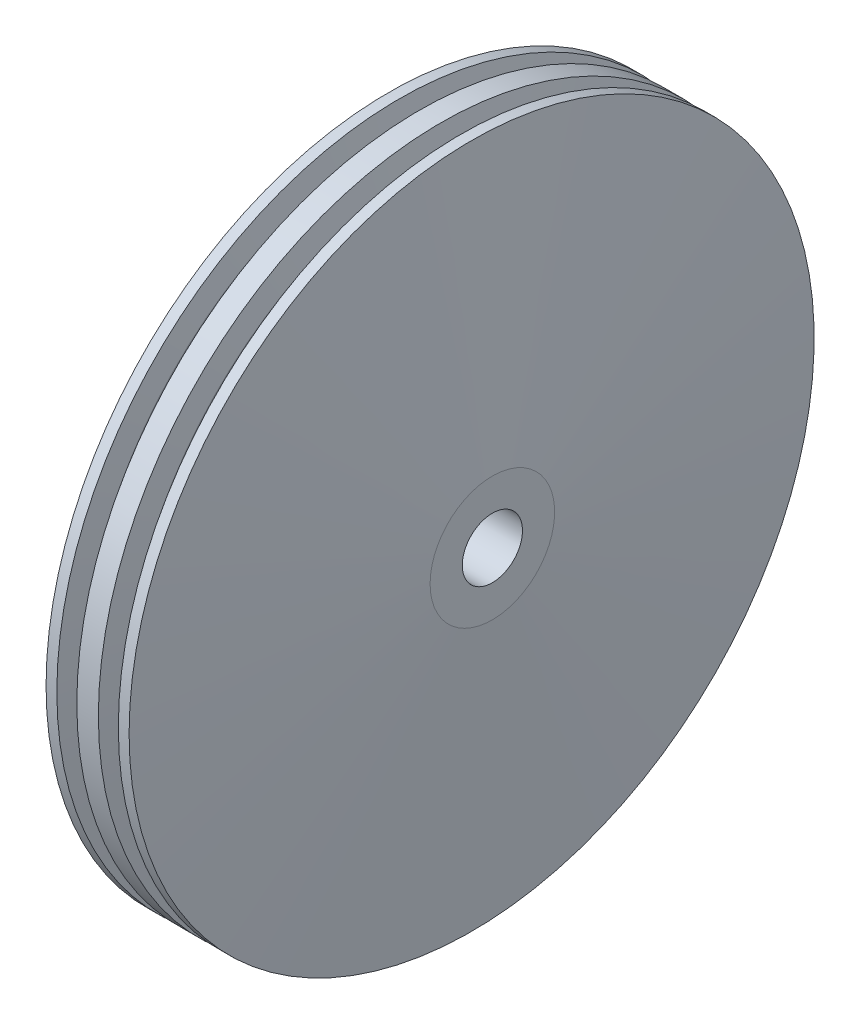
SolidWorks part; units mm, degrees
ref_plane "Plan de face" through (0, 0, 0) normal (0, 0, 1) x (1, 0, 0)
ref_plane "Plan de dessus" through (0, 0, 0) normal (0, 1, 0) x (1, 0, 0)
ref_plane "Plan de droite" through (0, 0, 0) normal (1, 0, 0) x (0, 0, -1)
sketch "Esquisse1" plane through (0, 0, 0) normal (0, 0, 1) x (1, 0, 0)
  line L0 (-34.8671, 0) -> (49.1442, 0) construction
  line L1 (1.7, 2.9) -> (1.7, 1.5)
  line L2 (1.7, 1.5) -> (-2.3, 1.5)
  line L3 (-2.3, 1.5) -> (-2.3, 2.9)
  line L4 (-2.3, 2.9) -> (-6, 2.9)
  line L5 (-6, 2.9) -> (-6, 6)
  line L6 (-6, 6) -> (-4, 33)
  line L7 (-4, 33) -> (-2.9619, 33)
  line L8 (-2.9619, 33) -> (-2.5909, 30.8958)
  line L9 (-1.4091, 30.8958) -> (-1.0381, 33)
  line L10 (-1.0381, 33) -> (1.0381, 33)
  line L11 (1.4091, 30.8958) -> (1.0381, 33)
  line L12 (2.5909, 30.8958) -> (2.9619, 33)
  line L13 (2.9619, 33) -> (4, 33)
  line L14 (4, 33) -> (6, 6)
  line L15 (6, 6) -> (6, 2.9)
  line L16 (6, 2.9) -> (1.7, 2.9)
  line L17 (0, 0) -> (0, 41.2601) construction
  line L18 (2, 31) -> (2, 38.3771) construction
  arc A0 (-2.5909, 30.8958) -> (-1.4091, 30.8958) centre (-2, 31) ccw
  arc A1 (1.4091, 30.8958) -> (2.5909, 30.8958) centre (2, 31) ccw
  dimension "D1" = 62
  dimension "D4" = 0.6
  dimension "D2" = 2
  dimension "D3" = 4
  dimension "D5" = 20
  dimension "D6" = 4
  dimension "D7" = 2
  dimension "D8" = 12
  dimension "D9" = 5.8
  dimension "D10" = 3
  dimension "D11" = 3.7
  dimension "D12" = 4
revolve "Révolution1" add sketch "Esquisse1" angle 360 about L0
